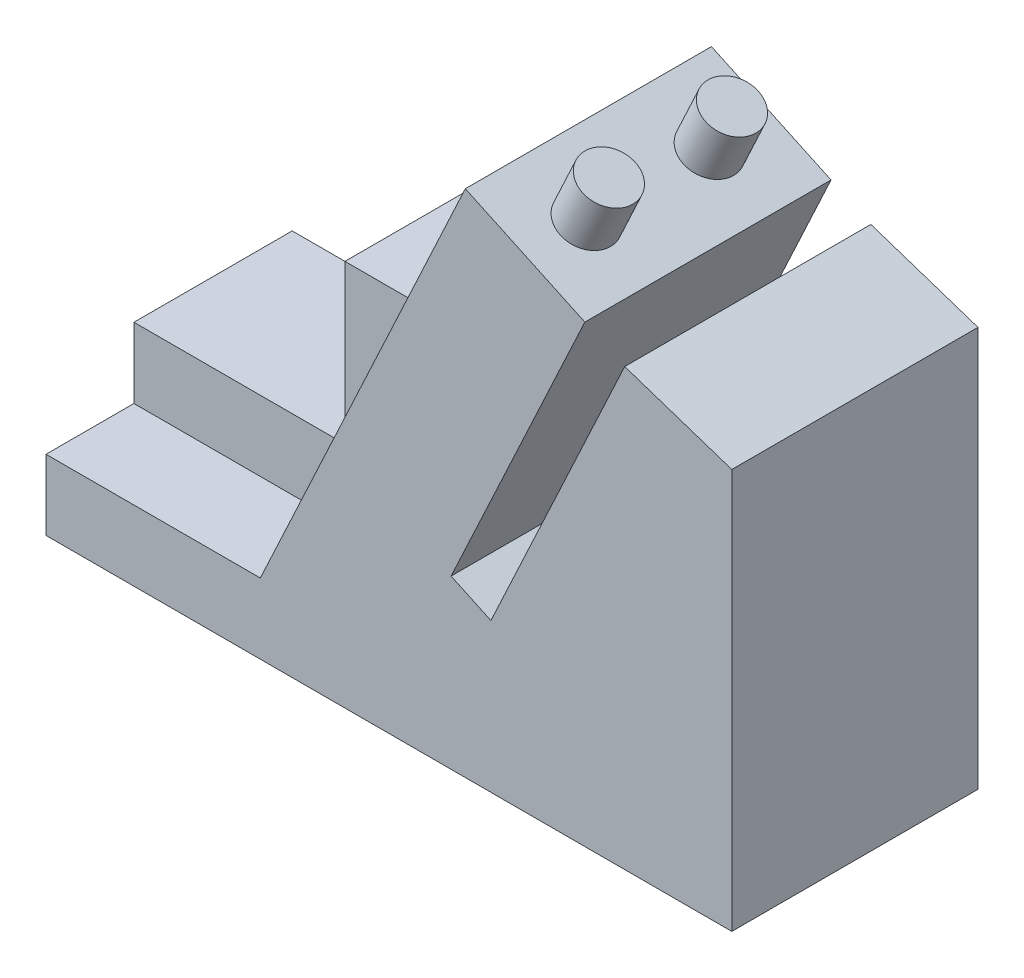
SolidWorks part; units mm, degrees
ref_plane "Front Plane" through (0, 0, 0) normal (0, 0, 1) x (1, 0, 0)
ref_plane "Top Plane" through (0, 0, 0) normal (0, 1, 0) x (1, 0, 0)
ref_plane "Right Plane" through (0, 0, 0) normal (1, 0, 0) x (0, 0, -1)
sketch "Sketch1" plane through (0, 0, 0) normal (0, 0, 1) x (1, 0, 0)
  line L0 (0, 0) -> (0, 45.5)
  line L1 (0, 0) -> (-78, 0)
  line L2 (-78, 0) -> (-78, 16)
  line L3 (-78, 16) -> (-54, 16)
  line L4 (-54, 16) -> (-54, 34)
  line L5 (-54, 34) -> (-41.5006, 34)
  line L6 (-53.6246, 8) -> (-30.3093, 58)
  line L7 (-30.3093, 58) -> (-16.7146, 51.6607)
  line L8 (-16.7146, 51.6607) -> (-31.9289, 19.0336)
  line L9 (-78, 8) -> (-53.6246, 8)
  line L10 (-31.9289, 19.0336) -> (-27.3974, 16.9206)
  line L11 (-27.3974, 16.9206) -> (-12.1831, 49.5476)
  line L12 (-16.7146, 51.6607) -> (-12.1831, 49.5476) construction
  line L13 (0, 45.5) -> (-12.1831, 49.5476)
  point P12 (-30.3093, 58)
  dimension "D1" = 45.5
  dimension "D2" = 78
  dimension "D3" = 16
  dimension "D4" = 24
  dimension "D5" = 34
  dimension "D6" = 58
  dimension "D7" = 65
  dimension "D8" = 12.4994
  dimension "D9" = 90
  dimension "D10" = 15
  dimension "D11" = 5
  dimension "D12" = 36
extrude "Boss-Extrude1" add sketch "Sketch1" along normal blind 28 contours L0 L13 L11 L10 L8 L7 L6 L9 L2 L1 region at (-39, 0.972, 0)
extrude "Boss-Extrude2" add sketch "Sketch1<4>" along normal blind 18 contours L2 L9 L6 L5 L4 L3 region at (-77.5519, 12, 0)
sketch "Sketch1<4>" plane through (0, 0, 0) normal (0, 0, 1) x (1, 0, 0) same geometry as "Sketch1"
ref_plane "Plane1" through (16.8019, 36.0317, 0) normal (0.4226, 0.9063, 0) x (0.9063, -0.4226, 0)
sketch "Sketch4" plane through (16.8019, 36.0317, 0) normal (0.4226, 0.9063, 0) x (0.9063, -0.4226, 0)
  line L6 (-51.9814, -28) -> (-51.9814, 0) construction
  circle A0 centre (-44.4814, -21) radius 3
  circle A1 centre (-44.4814, -7) radius 3
  point P18 (-47.1068, -28)
  dimension "D1" = 6
  dimension "D4" = 44.4814
  dimension "D2" = 7.5
  dimension "D3" = 7
  dimension "D5" = 7
extrude "Boss-Extrude3" add sketch "Sketch4" along normal blind 6
